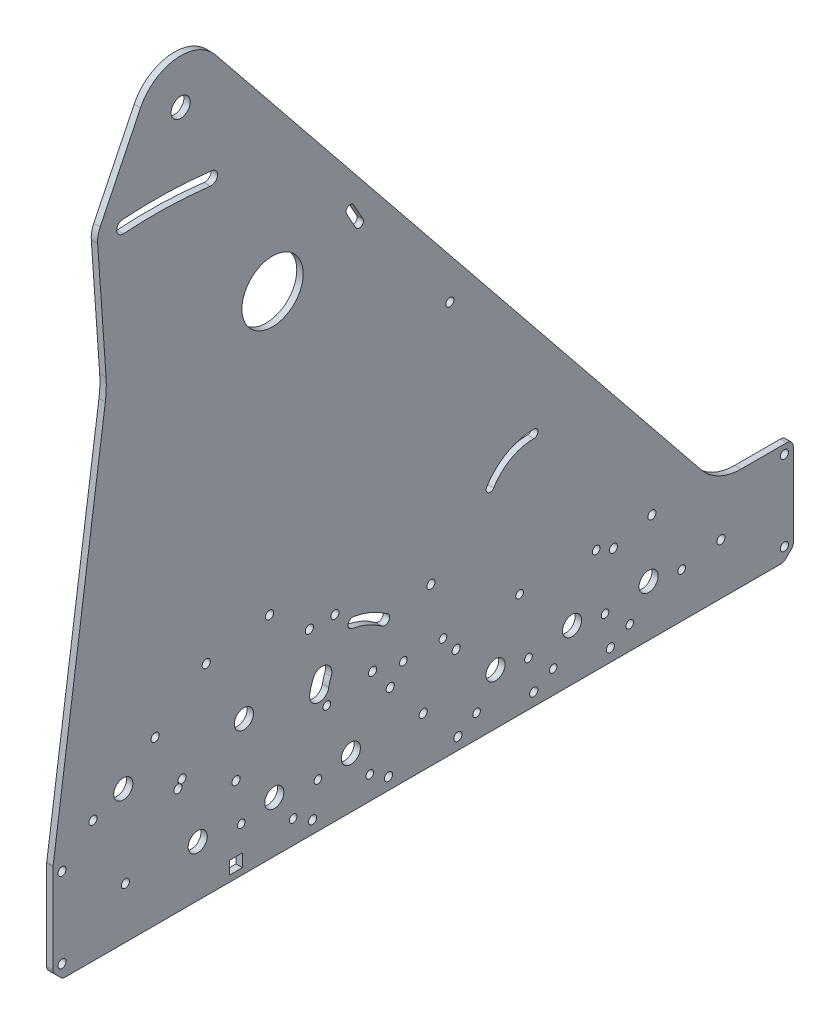
SolidWorks part; units mm, degrees
ref_plane "Front Plane" through (0, 0, 0) normal (0, 0, 1) x (1, 0, 0)
ref_plane "Top Plane" through (0, 0, 0) normal (0, 1, 0) x (1, 0, 0)
ref_plane "Right Plane" through (0, 0, 0) normal (1, 0, 0) x (0, 0, -1)
sketch "Sketch1" plane through (0, 0, 0) normal (1, 0, 0) x (0, 0, -1)
  line L0 (-184.15, -24.6062) -> (184.15, -24.6062)
  line L1 (184.15, -24.6062) -> (184.15, 26.1938)
  line L2 (184.15, 26.1938) -> (146.05, 26.1937)
  line L5 (-142.6632, 324.5299) -> (-184.15, 26.1938)
  line L6 (-184.15, 26.1938) -> (-184.15, -24.6062)
  line L7 (-184.15, 350.0437) -> (184.15, 350.0437) construction
  line L9 (146.05, 26.1937) -> (-103.3504, 335.4213)
  arc A0 (-103.3504, 335.4213) -> (-142.6632, 324.5299) centre (-120.65, 321.4687) ccw
  point P8 (0, -24.6062)
  dimension "D1" = 368.3
  dimension "D7" = 44.45
  dimension "D2" = 50.8
  dimension "D3" = 38.1
  dimension "D4" = 24.6062
  dimension "D5" = 374.65
  dimension "D6" = 304.8
  dimension "D8" = 346.075
extrude "Boss-Extrude1" add sketch "Sketch1" along normal blind 3.175
chamfer "Chamfer1" distance 4.7625 angle 45 2 edges at (1.5875, -24.6062, 184.15) (1.5875, -24.6062, -184.15)
fillet "Fillet1" radius 25.4 1 edges at (1.5875, 26.1937, -146.05)
fillet "Fillet2" radius 3.175 2 edges at (1.5875, 26.1938, 184.15) (1.5875, 26.1938, -184.15)
fillet "Fillet3" radius 3.175 4 edges at (1.5875, -19.8438, -184.15) (1.5875, -24.6062, -179.3875) (1.5875, -19.8437, 184.15) (1.5875, -24.6062, 179.3875)
sketch "Sketch30" plane through (3.175, 0, 0) normal (1, 0, 0) x (0, 0, -1)
  circle A8 centre (-89.211, 42.2593) radius 4.7625
  circle A9 centre (-25.1593, 30.6938) radius 2.032
  arc A10 (-51.7173, 35.4892) -> (-50.2741, 40.5715) centre (-25.1593, 30.6938) cw construction
  arc A11 (-54.7652, 42.3379) -> (-56.4665, 36.3468) centre (-25.1593, 30.6938) ccw
  arc A12 (-45.783, 38.8051) -> (-46.9681, 34.6317) centre (-25.1593, 30.6938) ccw
  arc A13 (-45.783, 38.8051) -> (-54.7652, 42.3379) centre (-50.2741, 40.5715) ccw
  arc A14 (-56.4665, 36.3468) -> (-46.9681, 34.6317) centre (-51.7173, 35.4892) ccw
  arc A15 (-34.9881, 56.6661) -> (-19.1131, 49.8125) centre (-41.7582, 19.1724) cw construction
  arc A16 (-17.6789, 51.753) -> (-34.5594, 59.0407) centre (-41.7582, 19.1724) ccw
  arc A17 (-20.5473, 47.8719) -> (-35.4169, 54.2915) centre (-41.7582, 19.1724) ccw
  arc A18 (-20.5473, 47.8719) -> (-17.6789, 51.753) centre (-19.1131, 49.8125) ccw
  arc A19 (-34.5594, 59.0407) -> (-35.4169, 54.2915) centre (-34.9881, 56.6661) ccw
  arc A20 (-19.1131, 49.8125) -> (-34.9881, 56.6661) centre (-41.7582, 19.1724) ccw construction
  circle A21 centre (94.6345, 23.8125) radius 2.032
  circle A22 centre (-56.6241, 64.5541) radius 2.032
  circle A23 centre (-43.9241, 64.5541) radius 2.032
  circle A24 centre (-56.6241, 64.5541) radius 1.905 construction
  circle A25 centre (-43.9241, 64.5541) radius 1.905 construction
  point P7 (-51.1204, 38.0658)
  point P19 (-26.6567, 54.1518)
  dimension "D2" = 9.652
  dimension "D4" = 4.064
  dimension "D1" = 4.064
  dimension ".375" = 9.525
  dimension "D3" = 4.826
extrude "Cut-Extrude9" cut sketch "Sketch30" against normal through all
sketch "Sketch16" plane through (3.175, 0, 0) normal (1, 0, 0) x (0, 0, -1)
  circle A0 centre (112.1746, 0.7937) radius 4.7625
  circle A1 centre (74.0746, 0.7937) radius 4.7625
  circle A2 centre (35.9746, 0.7937) radius 4.7625
  circle A3 centre (-35.9746, 0.7938) radius 4.7625
  circle A4 centre (-74.0746, 0.7938) radius 4.7625
  circle A5 centre (-112.1746, 0.7937) radius 4.7625
  dimension "D1" = 9.525
  dimension "D2" = 9.525
extrude "Cut-Extrude1" cut sketch "Sketch16" against normal up to next
sketch "Sketch25" plane through (3.175, 0, 0) normal (1, 0, 0) x (0, 0, -1)
  circle A0 centre (102.7672, -13.0003) radius 1.905 construction
  circle A1 centre (86.0486, 27.3622) radius 1.905 construction
  circle A2 centre (128.5804, -2.3081) radius 1.905 construction
  circle A3 centre (102.7672, -13.0003) radius 1.905
  circle A4 centre (86.0486, 27.3622) radius 1.905
  circle A5 centre (128.5804, -2.3081) radius 1.905
  circle A6 centre (64.6672, -13.0003) radius 1.905 construction
  circle A8 centre (-9.8486, 27.3622) radius 1.905 construction
  circle A10 centre (-47.9486, 27.3622) radius 1.905 construction
  circle A11 centre (-90.4804, -2.3081) radius 1.905 construction
  circle A12 centre (-64.6672, -13.0003) radius 1.905 construction
  circle A14 centre (-52.3804, -2.3081) radius 1.905 construction
  circle A15 centre (-26.5672, -13.0003) radius 1.905 construction
  circle A16 centre (9.8486, 27.3622) radius 1.905 construction
  circle A17 centre (26.5672, -13.0003) radius 1.905 construction
  circle A18 centre (47.9486, 27.3622) radius 1.905 construction
  circle A19 centre (52.3804, -2.3081) radius 1.905 construction
  circle A20 centre (90.4804, -2.3081) radius 1.905 construction
  circle A21 centre (-9.8486, 27.3622) radius 1.905
  circle A23 centre (-47.9486, 27.3622) radius 1.905
  circle A24 centre (-90.4804, -2.3081) radius 1.905
  circle A25 centre (-64.6672, -13.0003) radius 1.905
  circle A27 centre (-52.3804, -2.3081) radius 1.905
  circle A28 centre (-26.5672, -13.0003) radius 1.905
  circle A29 centre (9.8486, 27.3622) radius 1.905
  circle A30 centre (26.5672, -13.0003) radius 1.905
  circle A31 centre (47.9486, 27.3622) radius 1.905
  circle A32 centre (64.6672, -13.0003) radius 1.905
  circle A33 centre (52.3804, -2.3081) radius 1.905
  circle A34 centre (90.4804, -2.3081) radius 1.905
extrude "Cut-Extrude4" cut sketch "Sketch25" against normal up to next
sketch "Sketch23" plane through (3.175, 0, 0) normal (1, 0, 0) x (0, 0, -1)
  circle A0 centre (179.705, 21.7488) radius 1.905 construction
  point P0 (-55.0246, -18.3223)
  point P6 (-93.1246, 17.5943)
  point P9 (-17.2515, -18.6426)
  point P12 (-16.4124, 19.3854)
  point P15 (16.4124, 19.3854)
  point P18 (17.2515, -18.6426)
  point P21 (55.0246, -18.3223)
  point P35 (3.8736, 53.6853)
  point P38 (113.7728, 28.6594)
  point P44 (-179.705, 21.7487)
  point P47 (-179.705, -18.0026)
  point P50 (179.705, 21.7488)
  point P53 (179.705, -18.0026)
  point P59 (93.1246, -18.3223)
  point P63 (-122.0103, 28.5049)
  point P66 (-164.29, 36.0603)
hole_wizard "#8 (0.16) Diameter Hole1" positions "Sketch23" profile "Sketch24" hole size "#8" standard "ANSI Inch" end condition up to next
sketch "Sketch24" plane through (3.175, -18.3223, 55.0246) normal (0, 1, 0) x (0, 0, -1)
  line L0 (0, 0) -> (0, 3.175)
  line L1 (0, 3.175) -> (2.032, 3.175)
  line L2 (2.032, 3.175) -> (2.032, 0)
  line L5 (2.032, 0) -> (0, 0)
  line L11 (0, -6.35) -> (0, 107.95) construction
  dimension "Thru Hole Dia." = 4.064
  dimension "Thru Hole Depth" = 3.175
sketch "Sketch22" plane through (3.175, 0, 0) normal (1, 0, 0) x (0, 0, -1)
  line L0 (-96.2996, -15.1473) -> (-89.9496, -15.1473) construction
  line L1 (-96.2996, -15.1473) -> (-89.9496, -15.1473)
  line L2 (-96.2996, -15.1473) -> (-96.2996, -21.4973)
  line L3 (-96.2996, -21.4973) -> (-89.9496, -21.4973)
  line L4 (-89.9496, -15.1473) -> (-89.9496, -21.4973)
  line L5 (-96.2996, -15.1473) -> (-89.9496, -21.4973) construction
  line L6 (-96.2996, -21.4973) -> (-89.9496, -15.1473) construction
  line L7 (-89.9496, -15.1473) -> (-89.9496, -19.8734) construction
  point P0 (-93.1246, -18.3223)
  dimension "D1" = 6.35
extrude "Cut-Extrude3" cut sketch "Sketch22" against normal up to next
sketch "Sketch21" plane through (3.175, 0, 0) normal (1, 0, 0) x (0, 0, -1)
  circle A0 centre (-148.1579, 0.7937) radius 2.032
  circle A2 centre (0, 0) radius 2.032
  circle A3 centre (148.1579, 0.7938) radius 2.032
  dimension "D1" = 4.064
extrude "Cut-Extrude2" cut sketch "Sketch21" against normal up to next
sketch "Sketch26" [suppressed] plane through (3.175, 0, 0) normal (1, 0, 0) x (0, 0, -1)
  line L0 (-145.839, 321.5609) -> (-184.1236, 26.3971) construction
  line L1 (-178.0724, -24.6062) -> (178.0724, -24.6062) construction
  circle A0 centre (-121.0218, 216.6937) radius 15.24
  dimension "D1" = 30.48
  dimension "D2" = 38.1
  dimension "D3" = 241.3
extrude "Cut-Extrude5" [suppressed] cut sketch "Sketch26" against normal through all
sketch "Sketch27" plane through (3.175, 0, 0) normal (1, 0, 0) x (0, 0, -1)
  circle A0 centre (-120.65, 321.4687) radius 4.7625
  dimension "D1" = 9.525
extrude "Cut-Extrude6" cut sketch "Sketch27" against normal through all
sketch "Sketch28" plane through (3.175, 0, 0) normal (1, 0, 0) x (0, 0, -1)
  line L0 (-120.65, 321.4687) -> (-103.9389, 280.2796) construction
  line L1 (-103.9389, 280.2796) -> (-86.9156, 261.4285) construction
  line L2 (-86.9156, 261.4285) -> (-90.8226, 249.3444) construction
  line L3 (-90.8226, 249.3444) -> (-94.7296, 237.2603) construction
  line L4 (-142.6632, 324.5299) -> (-184.1197, 26.4114) construction
  circle A0 centre (-94.7296, 237.2603) radius 2.032
  circle A1 centre (-90.8226, 249.3444) radius 2.032
  circle A2 centre (-86.9156, 261.4285) radius 2.0955
  circle A3 centre (-103.9389, 280.2796) radius 2.032
  dimension "D4" = 4.064
  dimension "D5" = 4.191
  dimension "D6" = 4.064
  dimension "D1" = 25.4
  dimension "D2" = 44.45
  dimension "D3" = 12.7
  dimension "D7" = 30
  dimension "D8" = 120
  dimension "D9" = 160
extrude "Cut-Extrude7" [suppressed] cut sketch "Sketch28" against normal through all
sketch "Sketch31" plane through (0, 0, 0) normal (-1, 0, 0) x (0, 0, 1)
extrude "Cut-Extrude10" [suppressed] cut sketch "Sketch31" against normal through all
sketch "Sketch34" plane through (0, 0, 0) normal (-1, 0, 0) x (0, 0, 1)
  line L3 (123.2042, 95.6381) -> (126.7027, 70.4802) construction
  line L4 (125.3426, 95.9355) -> (128.8411, 70.7775)
  line L5 (121.0658, 95.3407) -> (124.5642, 70.1828)
  line L6 (142.6632, 324.5299) -> (184.1197, 26.4114) construction
  arc A2 (125.3426, 95.9355) -> (121.0658, 95.3407) centre (123.2042, 95.6381) ccw
  arc A3 (124.5642, 70.1828) -> (128.8411, 70.7775) centre (126.7027, 70.4802) ccw
  point P9 (124.9534, 83.0591)
  dimension "D8" = 4.318
  dimension "D6" = 50.8
  dimension "D7" = 25.4
extrude "Cut-Extrude12" [suppressed] cut sketch "Sketch34" against normal through all
sketch "Sketch38" plane through (3.175, 0, 0) normal (1, 0, 0) x (0, 0, -1)
  line L0 (-184.15, 25.974) -> (-184.15, -18.5286) construction
  line L1 (-178.0724, -24.6062) -> (178.0724, -24.6062) construction
  circle A0 centre (-133.35, 56.3562) radius 2.032
  circle A1 centre (-149.225, 42.0687) radius 4.7625
  circle A2 centre (-107.95, 75.4062) radius 2.032
  dimension "D1" = 50.8
  dimension "D3" = 4.064
  dimension "D4" = 9.525
  dimension "D7" = 4.064
  dimension "D2" = 80.9625
  dimension "D5" = 15.875
  dimension "D6" = 14.2875
  dimension "D8" = 25.4
  dimension "D9" = 19.05
extrude "Cut-Extrude14" cut sketch "Sketch38" against normal through all
sketch "Sketch56" plane through (3.175, 0, 0) normal (1, 0, 0) x (0, 0, -1)
  line L0 (-133.35, 284.9563) -> (-133.35, 56.3562) construction
  line L1 (-149.2963, 284.3994) -> (-133.35, 56.3562) construction
  line L2 (-133.35, 56.3562) -> (-105.4907, 283.2523) construction
  arc A0 (-149.2963, 284.3994) -> (-105.4907, 283.2523) centre (-133.35, 56.3562) cw
  arc A1 (-142.7671, 191.0274) -> (-116.8976, 190.35) centre (-133.35, 56.3562) cw
  dimension "D1" = 4
  dimension "D3" = 228.6
  dimension "D4" = 135
  dimension "D2" = 7
sketch "Sketch54" plane through (3.175, 0, 0) normal (1, 0, 0) x (0, 0, -1)
  line L0 (-142.6632, 324.5299) -> (-184.1197, 26.4114) construction
  line L1 (-140.6316, 331.1994) -> (-160.7144, 289.9597)
  line L2 (-142.6632, 324.5299) -> (-157.4154, 218.4453)
  line L3 (-140.6316, 331.1994) -> (-217.348, 331.1994) construction
  line L4 (-149.2963, 284.3994) -> (-133.35, 56.3562) construction
  line L5 (-161.9654, 283.5135) -> (-157.4154, 218.4453)
  arc A1 (-103.3504, 335.4213) -> (-142.6632, 324.5299) centre (-120.65, 321.4687) ccw construction
  arc A2 (-160.7144, 289.9597) -> (-161.9654, 283.5135) centre (-149.2963, 284.3994) ccw
  arc A3 (-140.6316, 331.1994) -> (-142.6632, 324.5299) centre (-120.65, 321.4687) ccw
  dimension "D1" = 12.7
extrude "Boss-Extrude2" add sketch "Sketch54" against normal up to surface (3.175 mm away) up to face at (0, 75.4062, 105.918)
sketch "Sketch57" plane through (3.175, 0, 0) normal (1, 0, 0) x (0, 0, -1)
  line L0 (138.4249, 35.6479) -> (-103.3504, 335.4213) construction
  arc A0 (-149.2963, 284.3994) -> (-105.4907, 283.2523) centre (-133.35, 56.3562) cw construction
  arc A1 (-105.1037, 286.4036) -> (-149.5178, 287.5667) centre (-133.35, 56.3562) ccw
  arc A2 (-105.8776, 280.101) -> (-149.0749, 281.2321) centre (-133.35, 56.3562) ccw
  arc A3 (-105.8776, 280.101) -> (-105.1037, 286.4036) centre (-105.4907, 283.2523) ccw
  arc A4 (-149.5178, 287.5667) -> (-149.0749, 281.2321) centre (-149.2963, 284.3994) ccw
  arc A5 (-105.4907, 283.2523) -> (-149.2963, 284.3994) centre (-133.35, 56.3562) ccw construction
  arc A6 (-142.7671, 191.0274) -> (-116.8976, 190.35) centre (-133.35, 56.3562) cw construction
  arc A7 (-116.5107, 193.5013) -> (-142.9886, 194.1947) centre (-133.35, 56.3562) ccw construction
  arc A8 (-117.2846, 187.1986) -> (-142.5456, 187.8601) centre (-133.35, 56.3562) ccw construction
  arc A9 (-117.2846, 187.1986) -> (-116.5107, 193.5013) centre (-116.8976, 190.35) ccw construction
  arc A10 (-142.9886, 194.1947) -> (-142.5456, 187.8601) centre (-142.7671, 191.0274) ccw construction
  circle A11 centre (13.2774, 170.5867) radius 2.032
  point P3 (-127.3659, 284.8779)
  point P16 (-129.8161, 191.31)
  dimension "D1" = 6.35
  dimension "D2" = 4.064
  dimension "D3" = 12.7
  dimension "D4" = 130.175
extrude "Cut-Extrude26" cut sketch "Sketch57" against normal up to next
sketch "Sketch37" plane through (3.175, 0, 0) normal (1, 0, 0) x (0, 0, -1)
  line L0 (55.0742, 92.9044) -> (63.2984, 92.9044) construction
  arc A1 (33.3375, 80.645) -> (55.0742, 92.9044) centre (55.0742, 67.5044) cw construction
  arc A2 (55.0742, 94.9364) -> (31.5986, 81.6962) centre (55.0742, 67.5044) ccw
  arc A3 (55.0742, 90.8724) -> (35.0764, 79.5938) centre (55.0742, 67.5044) ccw
  arc A4 (55.0742, 90.8724) -> (55.0742, 94.9364) centre (55.0742, 92.9044) ccw
  arc A5 (31.5986, 81.6962) -> (35.0764, 79.5938) centre (33.3375, 80.645) ccw
  circle A8 centre (0, 0) radius 2.032 construction
  point P4 (42.5965, 89.6283)
  dimension "D1" = 25.4
  dimension "D4" = 24.9555
  dimension "D5" = 2.032
  dimension "D2" = 33.3375
  dimension "D3" = 80.645
extrude "Cut-Extrude13" cut sketch "Sketch37" against normal through all
sketch "Sketch40" plane through (3.175, 0, 0) normal (1, 0, 0) x (0, 0, -1)
  circle A0 centre (-120.015, 31.75) radius 2.032
  dimension "D1" = 4.064
  dimension "D2" = 120.015
  dimension "D3" = 31.75
extrude "Cut-Extrude16" cut sketch "Sketch40" against normal through all
sketch "Sketch41" [suppressed] plane through (3.175, 0, 0) normal (1, 0, 0) x (0, 0, -1)
  line L0 (-120.65, 318.2937) -> (-98.425, 279.7989) construction
  line L1 (-98.425, 279.7989) -> (-77.6666, 265.1617) construction
  line L2 (-120.65, 318.2937) -> (-60.41, 318.2937) construction
  circle A0 centre (-120.65, 318.2937) radius 25.4 construction
  circle A1 centre (-98.425, 279.7989) radius 19.05 construction
  circle A2 centre (-77.6666, 265.1617) radius 6.35 construction
  circle A3 centre (-98.425, 279.7989) radius 2.032
  circle A4 centre (-77.6666, 265.1617) radius 2.032
  dimension "D1" = 50.8
  dimension "D2" = 38.1
  dimension "D3" = 12.7
  dimension "D4" = 4.064
  dimension "D5" = 60
extrude "Cut-Extrude17" [suppressed] cut sketch "Sketch41" against normal through all
sketch "Sketch43" plane through (3.175, 0, 0) normal (1, 0, 0) x (0, 0, -1)
  line L0 (-152.4, 200.025) -> (-123.6487, 200.025) construction
  line L1 (-115.9779, 252.0412) -> (-152.4, 200.025) construction
  circle A0 centre (-152.4, 200.025) radius 2.032
  arc A1 (-143.2813, 262.8669) -> (-96.4668, 230.087) centre (-152.4, 200.025) cw construction
  arc A2 (-92.2158, 232.3717) -> (-142.5883, 267.6428) centre (-152.4, 200.025) ccw
  arc A3 (-100.7177, 227.8023) -> (-143.9743, 258.0909) centre (-152.4, 200.025) ccw
  arc A4 (-100.7177, 227.8023) -> (-92.2158, 232.3717) centre (-96.4668, 230.087) ccw
  arc A5 (-142.5883, 267.6428) -> (-143.9743, 258.0909) centre (-143.2813, 262.8669) ccw
  point P6 (-115.9779, 252.0412)
  dimension "D1" = 4.064
  dimension "D4" = 4.826
  dimension "D2" = 200.025
  dimension "D3" = 152.4
  dimension "D5" = 63.5
  dimension "D6" = 57.15
  dimension "D7" = 55
extrude "Cut-Extrude19" [suppressed] cut sketch "Sketch43" against normal through all
sketch "Sketch44" plane through (3.175, 0, 0) normal (1, 0, 0) x (0, 0, -1)
  circle A0 centre (-142.875, 226.3775) radius 2.032
  dimension "D1" = 4.064
  dimension "D2" = 142.875
  dimension "D3" = 226.3775
extrude "Cut-Extrude20" [suppressed] cut sketch "Sketch44" against normal through all
sketch "Sketch50" plane through (0, 0, 0) normal (-1, 0, 0) x (0, 0, 1)
  line L0 (89.6567, 207.1688) -> (64.2567, 207.1688) construction
  line L1 (89.6567, 205.1368) -> (64.2567, 205.1368)
  line L2 (89.6567, 209.2008) -> (64.2567, 209.2008)
  line L3 (64.2567, 194.4688) -> (38.8567, 194.4688) construction
  line L4 (64.2567, 192.4368) -> (38.8567, 192.4368)
  line L5 (64.2567, 196.5008) -> (38.8567, 196.5008)
  arc A1 (89.6567, 205.1368) -> (89.6567, 209.2008) centre (89.6567, 207.1688) ccw
  arc A2 (64.2567, 209.2008) -> (64.2567, 205.1368) centre (64.2567, 207.1688) ccw
  arc A3 (64.2567, 192.4368) -> (64.2567, 196.5008) centre (64.2567, 194.4688) ccw
  arc A4 (38.8567, 196.5008) -> (38.8567, 192.4368) centre (38.8567, 194.4688) ccw
  point P3 (76.9567, 207.1688)
  point P5 (51.5567, 194.4688)
  dimension "D1" = 2.032
  dimension "D2" = 207.1688
  dimension "D3" = 89.6567
  dimension "D4" = 25.4
  dimension "D5" = 12.7
extrude "Cut-Extrude22" [suppressed] cut sketch "Sketch50" against normal through all
sketch "Sketch51" plane through (3.175, 0, 0) normal (1, 0, 0) x (0, 0, -1)
  circle A0 centre (-111.125, 222.6469) radius 2.032
  circle A1 centre (-111.125, 190.8969) radius 2.032
  dimension "D1" = 222.6469
  dimension "D3" = 31.75
  dimension "D4" = 4.064
  dimension "D2" = 111.125
extrude "Cut-Extrude23" [suppressed] cut sketch "Sketch51" against normal through all
sketch "Sketch52" [suppressed] plane through (0, 0, 0) normal (-1, 0, 0) x (0, 0, 1)
  line L0 (145.839, 321.5609) -> (184.1236, 26.3971) construction
  line L1 (142.875, 226.3775) -> (142.0856, 251.7652) construction
  line L2 (120.4939, 238.3877) -> (142.875, 226.3775) construction
  arc A5 (142.0856, 251.7652) -> (120.4939, 238.3877) centre (142.875, 226.3775) ccw construction
  arc A6 (142.0224, 253.7962) -> (118.7034, 239.3485) centre (142.875, 226.3775) ccw
  arc A7 (142.1487, 249.7342) -> (122.2844, 237.4269) centre (142.875, 226.3775) ccw
  arc A8 (142.1487, 249.7342) -> (142.0224, 253.7962) centre (142.0856, 251.7652) ccw
  arc A9 (118.7034, 239.3485) -> (122.2844, 237.4269) centre (120.4939, 238.3877) ccw
  point P4 (129.4975, 247.9692)
  dimension "D1" = 25.4
  dimension "D2" = 2.032
  dimension "D3" = 12.7
  dimension "D4" = 60
extrude "Cut-Extrude24" [suppressed] cut sketch "Sketch52" against normal through all
sketch "Sketch53" plane through (3.175, 0, 0) normal (1, 0, 0) x (0, 0, -1)
  line L0 (-25.4, 197.2663) -> (-25.4, 135.876) construction
  line L1 (-23.368, 197.2663) -> (-23.368, 135.876)
  line L2 (-27.432, 197.2663) -> (-27.432, 135.876)
  arc A0 (-23.368, 197.2663) -> (-27.432, 197.2663) centre (-25.4, 197.2663) ccw
  arc A1 (-27.432, 135.876) -> (-23.368, 135.876) centre (-25.4, 135.876) ccw
  point P2 (-25.4, 166.5712)
  dimension "D1" = 2.032
  dimension "D2" = 61.3903
  dimension "D3" = 197.2663
  dimension "D4" = 25.4
extrude "Cut-Extrude25" [suppressed] cut sketch "Sketch53" against normal through all
sketch "Sketch58" plane through (3.175, 0, 0) normal (1, 0, 0) x (0, 0, -1)
  line L0 (138.4249, 35.6479) -> (-103.3504, 335.4213) construction
  line L1 (-74.9571, 219.298) -> (-112.7732, 223.9412) construction
  line L2 (-133.35, 56.3562) -> (-105.4907, 283.2523) construction
  circle A0 centre (-74.9571, 219.298) radius 15.24
  dimension "D1" = 50.8
  dimension "D2" = 30.48
  dimension "D3" = 38.1
extrude "Cut-Extrude27" cut sketch "Sketch58" against normal through all
sketch "Sketch60" [suppressed] plane through (0, 0, 0) normal (-1, 0, 0) x (0, 0, 1)
  line L1 (-37.547, 154.5028) -> (64.3989, 263.8478) construction
  line L2 (120.65, 321.4687) -> (120.65, 283.4951) construction
  line L3 (-17.6374, 138.8786) -> (63.8163, 263.1055) construction
  line L4 (113.0282, 299.2883) -> (107.0925, 303.8578) construction
  line L5 (65.8258, 264.9495) -> (112.2759, 289.9949) construction
  line L7 (120.65, 321.4687) -> (120.65, 359.4144) construction
  line L8 (120.65, 321.4687) -> (109.6389, 294.8856) construction
  line L10 (120.65, 321.4687) -> (-169.232, 227.2804) construction
  line L11 (120.65, 321.4687) -> (354.1403, 125.5471) construction
  line L12 (64.8747, 264.3011) -> (106.0507, 299.1279) construction
  line L13 (110.3554, 300.3954) -> (117.7837, 299.4293) construction
  line L14 (-16.0993, 160.9177) -> (-13.2774, 170.5867) construction
  circle A7 centre (74.9571, 219.298) radius 33.3375 construction
  circle A10 centre (68.4628, 260.0588) radius 2.032
  circle A11 centre (68.4628, 260.0588) radius 7.9375 construction
  circle A15 centre (-28.258, 145.8423) radius 1.778
  circle A17 centre (120.65, 321.4687) radius 22.225 construction
  circle A20 centre (109.6389, 294.8856) radius 6.5484 construction
  circle A21 centre (109.6389, 294.8856) radius 2.032
  circle A22 centre (109.6389, 294.8856) radius 5.5563 construction
  circle A23 centre (68.4628, 260.0588) radius 5.5563 construction
  circle A24 centre (-28.258, 145.8423) radius 12.7 construction
  arc A25 (-44.7806, 147.1408) -> (-23.4901, 129.9695) centre (-28.258, 145.8423) ccw construction
  circle A26 centre (-16.0993, 160.9177) radius 2.032
  circle A27 centre (-35.0103, 118.6566) radius 2.032
  circle A28 centre (-53.3973, 133.4862) radius 2.032
  circle A31 centre (-16.0993, 160.9177) radius 1.905 construction
  circle A32 centre (-35.0103, 118.6566) radius 1.905 construction
  circle A33 centre (-53.3973, 133.4862) radius 1.905 construction
  dimension "D4" = 11.1125
  dimension "D3" = 13.0969
  dimension "D6" = 66.675
  dimension "D7" = 4.064
  dimension "D8" = 4.064
  dimension "D2" = 22.5
  dimension "D9" = 15.875
  dimension "D5" = 44.45
  dimension "D15" = 25.4
  dimension "D10" = 3.556
  dimension "D11" = 108
  dimension "D12" = 130
  dimension "D13" = 304.8
  dimension "D14" = 304.8
extrude "Cut-Extrude28" [suppressed] cut sketch "Sketch60" against normal through all
fillet "Fillet4" radius 50.8 1 edges at (1.5875, 218.4453, 157.4154)
sketch "Sketch62" plane through (0, 0, 0) normal (-1, 0, 0) x (0, 0, 1)
  line L3 (31.75, 227.0125) -> (36.3514, 235.3523) construction
  line L4 (29.9708, 227.9941) -> (34.5722, 236.334)
  line L5 (33.5292, 226.0309) -> (38.1306, 234.3707)
  line L6 (-138.4249, 35.6479) -> (103.3504, 335.4213) construction
  arc A6 (29.9708, 227.9941) -> (33.5292, 226.0309) centre (31.75, 227.0125) ccw
  arc A7 (38.1306, 234.3707) -> (34.5722, 236.334) centre (36.3514, 235.3523) ccw
  point P3 (34.0507, 231.1824)
  dimension "D1" = 31.75
  dimension "D3" = 9.525
  dimension "D4" = 2.032
  dimension "D2" = 227.0125
  dimension "D5" = 10
extrude "Cut-Extrude30" cut sketch "Sketch62" against normal through all
sketch "Sketch63" plane through (3.175, 0, 0) normal (1, 0, 0) x (0, 0, -1)
  circle A0 centre (-76.4451, 80.645) radius 2.032
  dimension "D1" = 4.064
  dimension "D2" = 80.645
  dimension "D3" = 76.4451
extrude "Cut-Extrude31" cut sketch "Sketch63" against normal through all
sketch "Sketch64" [suppressed] plane through (0, 0, 0) normal (-1, 0, 0) x (0, 0, 1)
  circle A0 centre (60.4309, 266.5368) radius 2.032
  circle A1 centre (60.4309, 266.5368) radius 1.905 construction
  circle A2 centre (78.1747, 256.5724) radius 2.032
  circle A3 centre (119.5608, 294.8856) radius 2.032
  circle A4 centre (78.1747, 256.5724) radius 1.905 construction
  circle A5 centre (119.5608, 294.8856) radius 1.905 construction
  dimension "D1" = 4.064
extrude "Cut-Extrude32" [suppressed] cut sketch "Sketch64" against normal up to next
